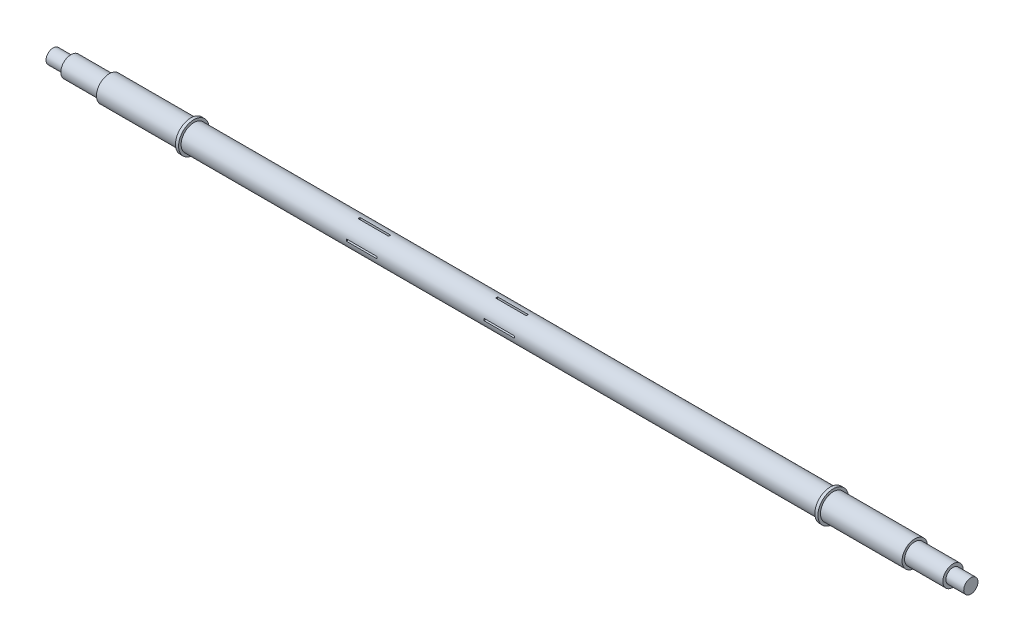
SolidWorks part; units mm, degrees
material "1.0045 (S355JR)"
ref_plane "Ön Düzlem" through (0, 0, 0) normal (0, 0, 1) x (1, 0, 0)
ref_plane "Üst Düzlem" through (0, 0, 0) normal (0, 1, 0) x (1, 0, 0)
ref_plane "Sağ Düzlem" through (0, 0, 0) normal (1, 0, 0) x (0, 0, -1)
sketch "Çizim1" plane through (0, 0, 0) normal (0, 0, 1) x (1, 0, 0)
  line L0 (0, 0) -> (0, 128.866) construction
  line L1 (450, 0) -> (450, 7)
  line L2 (450, 7) -> (432.5, 7)
  line L3 (432.5, 7) -> (432.5, 10)
  line L4 (432.5, 10) -> (395, 10)
  line L5 (395, 10) -> (395, 12.5)
  line L6 (-395, 10) -> (-395, 12.5)
  line L7 (-432.5, 10) -> (-395, 10)
  line L8 (-432.5, 7) -> (-432.5, 10)
  line L9 (-450, 7) -> (-432.5, 7)
  line L10 (-450, 0) -> (-450, 7)
  line L11 (-450, 0) -> (450, 0)
  line L12 (395, 12.5) -> (-395, 12.5)
  dimension "D2" = 7
  dimension "D3" = 17.5
  dimension "D4" = 3
  dimension "D5" = 37.5
  dimension "D6" = 2.5
revolve "Döndür1" add sketch "Çizim1" angle 360 about L11
sketch "Çizim2" plane through (0, 0, 0) normal (1, 0, 0) x (0, 0, -1)
  circle A0 centre (0, 0) radius 15
  dimension "D1" = 30
extrude "Yükseklik-Ekstrüzyon1" add sketch "Çizim2" along normal blind 3 from offset 315 offset against normal yes
extrude "Yükseklik-Ekstrüzyon2" add sketch "Çizim2<2>" against normal blind 3 from offset 315
sketch "Çizim2<2>" plane through (0, 0, 0) normal (1, 0, 0) x (0, 0, -1) same geometry as "Çizim2"
sketch "Çizim3" plane through (0, 0, 0) normal (0, 0, 1) x (1, 0, 0)
  line L0 (0, 0) -> (0, 120.0855) construction
  line L1 (0, 120.0855) -> (314, 120.0855) construction
  dimension "D1" = 314
sketch "Çizim4" plane through (0, 0, 0) normal (1, 0, 0) x (0, 0, -1)
  line L0 (12.5, 0) -> (1, 0) construction
  line L1 (-12.4599, 1) -> (-1, 1)
  line L2 (-12.4599, -1) -> (-1, -1)
  line L4 (1, 12.4599) -> (1, 1)
  line L5 (-1, 12.4599) -> (-1, 1)
  line L6 (-1, -1) -> (-1, -12.4599)
  line L7 (0, 1) -> (0, 12.5) construction
  line L8 (1, -1) -> (1, -12.4599)
  line L9 (1, 1) -> (12.4599, 1)
  line L10 (-1, 0) -> (-12.5, 0) construction
  line L11 (1, -1) -> (12.4599, -1)
  arc A7 (-1, -12.4599) -> (1, -12.4599) centre (0, 0) ccw
  arc A8 (-12.4599, 1) -> (-12.4599, -1) centre (0, 0) ccw
  arc A9 (1, 12.4599) -> (-1, 12.4599) centre (0, 0) ccw
  arc A10 (12.4599, -1) -> (12.4599, 1) centre (0, 0) ccw
  dimension "D2" = 1
extrude "Kes-Ekstrüzyon2" cut sketch "Çizim4" along normal mid plane 30
sketch "Çizim6" plane through (450, 0, 0) normal (1, 0, 0) x (0, 0, -1)
  line L93 (1, 1) -> (1, 12.4599)
  line L94 (12.4599, 1) -> (1, 1)
  line L95 (-1, 12.4599) -> (-1, 1)
  line L96 (-1, 1) -> (-12.4599, 1)
  line L97 (-12.4599, -1) -> (-1, -1)
  line L98 (-1, -1) -> (-1, -12.4599)
  line L99 (1, -12.4599) -> (1, -1)
  line L100 (1, -1) -> (12.4599, -1)
  line L101 (1, 1) -> (1, 12.4599)
  line L102 (12.4599, 1) -> (1, 1)
  line L103 (-1, 12.4599) -> (-1, 1)
  line L104 (-1, 1) -> (-12.4599, 1)
  line L105 (-12.4599, -1) -> (-1, -1)
  line L106 (-1, -1) -> (-1, -12.4599)
  line L107 (1, -12.4599) -> (1, -1)
  line L108 (1, -1) -> (12.4599, -1)
  arc A36 (-12.4599, 1) -> (-12.4599, -1) centre (0, 0) ccw
  arc A37 (-1, -12.4599) -> (1, -12.4599) centre (0, 0) ccw
  arc A38 (12.4599, -1) -> (12.4599, 1) centre (0, 0) ccw
  arc A39 (1, 12.4599) -> (-1, 12.4599) centre (0, 0) ccw
  arc A40 (-12.4599, 1) -> (-12.4599, -1) centre (0, 0) ccw
  arc A41 (-1, -12.4599) -> (1, -12.4599) centre (0, 0) ccw
  arc A42 (12.4599, -1) -> (12.4599, 1) centre (0, 0) ccw
  arc A43 (1, 12.4599) -> (-1, 12.4599) centre (0, 0) ccw
  dimension "D1" = 0
extrude "Kes-Ekstrüzyon3" cut sketch "Çizim6" against normal blind 30 from offset 570 offset against normal yes
